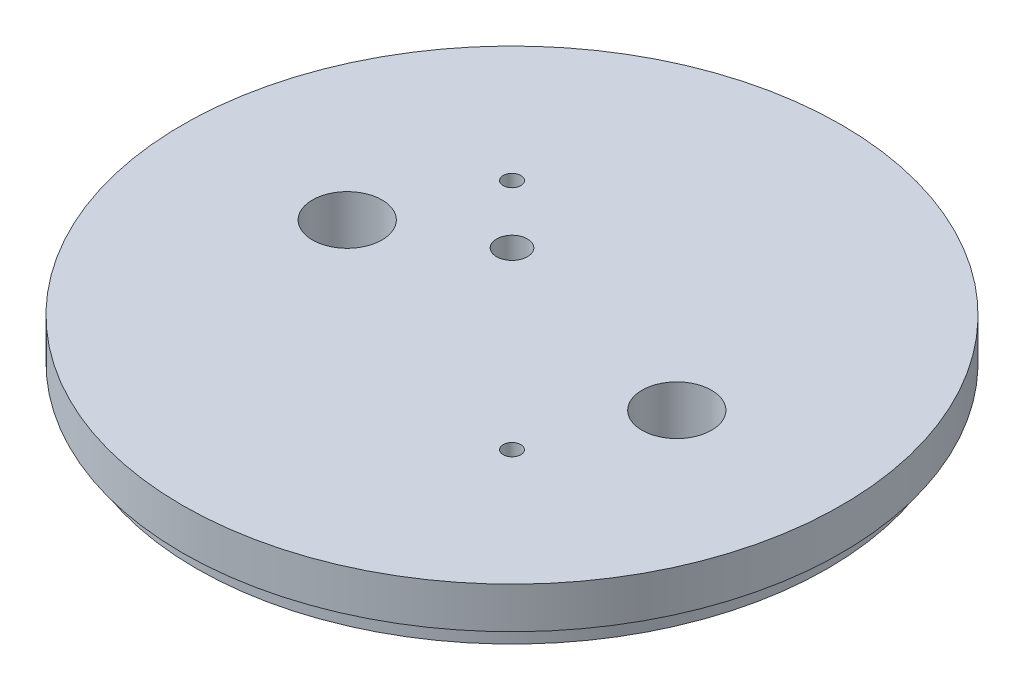
SolidWorks part; units mm, degrees
material "6061-T4 (SS)"
ref_plane "Front Plane" through (0, 0, 0) normal (0, 0, 1) x (1, 0, 0)
ref_plane "Top Plane" through (0, 0, 0) normal (0, 1, 0) x (1, 0, 0)
ref_plane "Right Plane" through (0, 0, 0) normal (1, 0, 0) x (0, 0, -1)
sketch "Sketch1" plane through (0, 0, 0) normal (0, 1, 0) x (1, 0, 0)
  line L0 (0, -50.8) -> (0, 50.8) construction
  line L1 (-50.8, 0) -> (50.8, 0) construction
  line L2 (-17.9605, 17.9605) -> (0, 0) construction
  line L3 (0, 56.7387) -> (0, 29.6936) construction
  line L4 (3.6407, 56.7387) -> (3.6407, 29.6936) construction
  line L5 (-3.6407, 56.7387) -> (-3.6407, 29.6936) construction
  line L6 (0, -56.7387) -> (0, -29.6936) construction
  line L7 (3.6407, -56.7387) -> (3.6407, -29.6936) construction
  line L8 (-3.6407, -56.7387) -> (-3.6407, -29.6936) construction
  line L9 (-35.921, -35.921) -> (54.3236, 54.3236) construction
  circle A0 centre (0, 0) radius 50.8
  circle A1 centre (0, 0) radius 3.175 construction
  circle A2 centre (25.4, 0) radius 5.3578
  circle A3 centre (-25.4, 0) radius 5.3578
  circle A4 centre (-17.9605, 17.9605) radius 1.3589
  arc A6 (3.6407, 56.7387) -> (-3.6407, 56.7387) centre (0, 56.7387) ccw construction
  arc A7 (-3.6407, 29.6936) -> (3.6407, 29.6936) centre (0, 29.6936) ccw construction
  arc A8 (3.6407, -56.7387) -> (-3.6407, -56.7387) centre (0, -56.7387) cw construction
  arc A9 (-3.6407, -29.6936) -> (3.6407, -29.6936) centre (0, -29.6936) cw construction
  circle A10 centre (17.9605, -17.9605) radius 1.3589
  circle A11 centre (-8.9803, 8.9803) radius 2.3813
  circle A12 centre (8.9803, -8.9803) radius 2.3813 construction
  point P16 (0, 43.2162)
  point P19 (0, 0)
  point P26 (0, -43.2162)
  dimension "D1" = 101.6
  dimension "D2" = 6.35
  dimension "D3" = 10.7156
  dimension "D5" = 2.7178
  dimension "D8" = 4.7625
  dimension "D6" = 25.4
  dimension "D7" = 45
  dimension "D4" = 45
  dimension "D9" = 25.4
extrude "Boss-Extrude1" add sketch "Sketch1" along normal blind 9.525
sketch "Sketch2" plane through (0, 0, 0) normal (0, -1, 0) x (1, 0, 0)
  circle A0 centre (0, 0) radius 50.8
  circle A1 centre (0, 0) radius 48.641
  dimension "D1" = 101.6
  dimension "D2" = 97.282
extrude "Cut-Extrude1" cut sketch "Sketch2" against normal blind 3.175
sketch "Sketch3" plane through (0, 9.525, 0) normal (0, 1, 0) x (1, 0, 0)
  line L0 (0, 50.8) -> (0, -50.8) construction
  line L1 (-50.8, 0) -> (50.8, 0) construction
  line L2 (0, 34.798) -> (0, 13.97) construction
  line L3 (3.2385, 34.798) -> (3.2385, 13.97)
  line L4 (-3.2385, 34.798) -> (-3.2385, 13.97)
  line L5 (0, -34.798) -> (0, -13.97) construction
  line L6 (3.2385, -34.798) -> (3.2385, -13.97)
  line L7 (-3.2385, -34.798) -> (-3.2385, -13.97)
  circle A0 centre (0, 0) radius 50.8 construction
  arc A1 (3.2385, 34.798) -> (-3.2385, 34.798) centre (0, 34.798) ccw
  arc A2 (-3.2385, 13.97) -> (3.2385, 13.97) centre (0, 13.97) ccw
  arc A3 (3.2385, -34.798) -> (-3.2385, -34.798) centre (0, -34.798) cw
  arc A4 (-3.2385, -13.97) -> (3.2385, -13.97) centre (0, -13.97) cw
  point P7 (0, 13.97)
  point P8 (0, 34.798)
  point P12 (0, 24.384)
  point P20 (0, -24.384)
  point P25 (0, -34.798)
  point P26 (0, -13.97)
  dimension "D1" = 13.97
  dimension "D2" = 20.828
  dimension "D3" = 6.477
extrude "Cut-Extrude2" cut sketch "Sketch3" against normal blind 3.556 from offset 5.969 offset against normal yes
equation "\"Coupler_OD\" = 3.899in"
equation "\"Coupler_ID\" = 3.755in"
equation "\"Lead_Screw_Hole_Diam\" = (27/64)*1in"
equation "\"Lead_Screw_Dist\" = 2in"
equation "\"D9@Sketch1\"=\"Lead_Screw_Dist\"/2"
equation "\"D3@Sketch1\"=\"Lead_Screw_Hole_Diam\""
